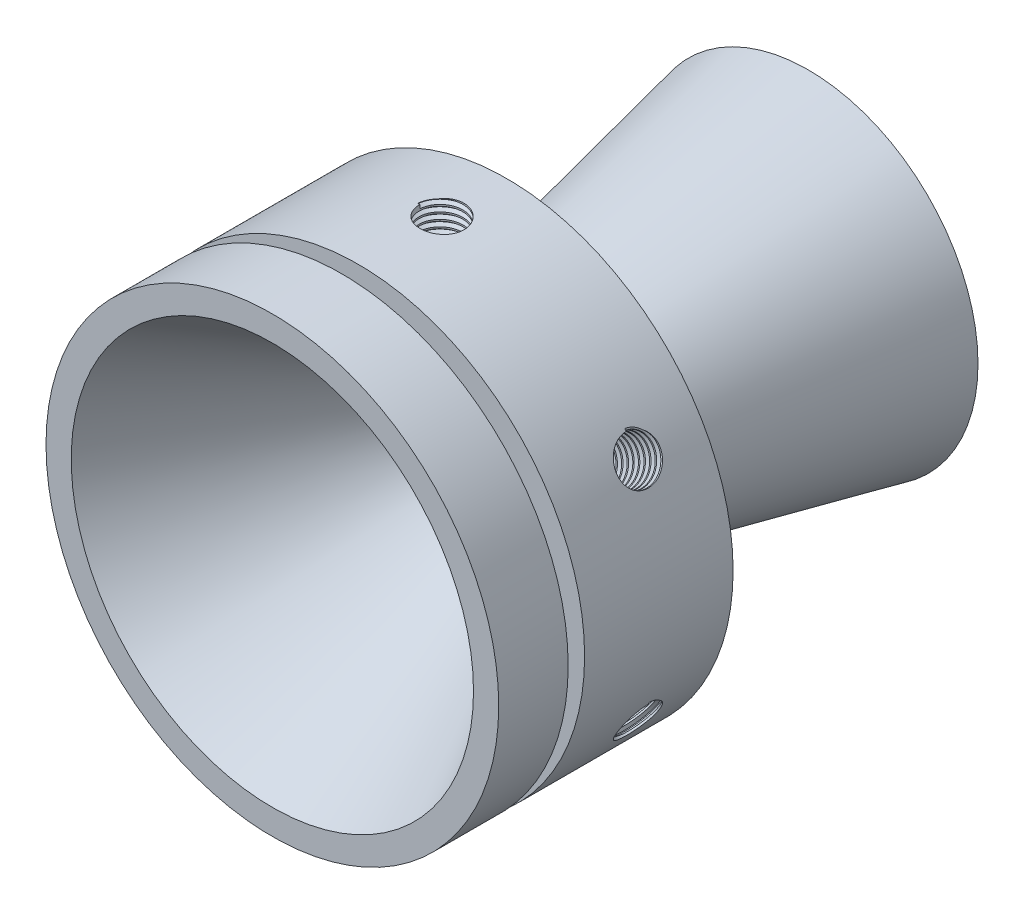
SolidWorks part; units mm, degrees
material "ASTM A53"
ref_plane "Alzado" through (0, 0, 0) normal (0, 0, 1) x (1, 0, 0)
ref_plane "Planta" through (0, 0, 0) normal (0, 1, 0) x (1, 0, 0)
ref_plane "Vista lateral" through (0, 0, 0) normal (1, 0, 0) x (0, 0, -1)
sketch "Croquis2" plane through (0, 0, 0) normal (1, 0, 0) x (0, 0, -1)
  line L0 (-14.0172, 0) -> (56.1534, 0) construction
  line L1 (0, 15.54) -> (18.1077, 5.0855)
  line L2 (18.1077, 5.0855) -> (42.0355, 10.1715)
  line L3 (0, 15.54) -> (0, 17.4892)
  line L4 (0, 17.4892) -> (5.365, 17.4892)
  line L5 (18.1077, 17.4892) -> (18.1077, 8.1525)
  line L6 (18.1077, 8.1525) -> (41.4117, 13.1059)
  line L7 (41.4117, 13.1059) -> (42.0355, 10.1715)
  line L8 (5.365, 17.4892) -> (5.365, 15.4572)
  line L9 (5.365, 15.4572) -> (6.635, 15.4572)
  line L10 (6.635, 15.4572) -> (6.635, 17.4892)
  line L11 (6.635, 17.4892) -> (18.1077, 17.4892)
  point P14 (6, 15.4572)
  point P15 (13.1077, 17.4892)
  dimension "D1" = 12
  dimension "D2" = 30
  dimension "D3" = 10.171
  dimension "D4" = 31.08
  dimension "D5" = 20.343
  dimension "D6" = 3
  dimension "D7" = 34.9784
  dimension "D8" = 6
  dimension "D9" = 2.032
  dimension "D10" = 1.27
  dimension "D11" = 5
revolve "Revolución1" add sketch "Croquis2" angle 360 about L0
ref_plane "Plano1" through (0, 17.4892, 0) normal (0, 1, 0) x (1, 0, 0)
sketch "Croquis3" plane through (0, 17.4892, 0) normal (0, 1, 0) x (1, 0, 0)
  line L0 (17.4892, 18.1077) -> (-17.4892, 18.1077) construction
  point P0 (0, 13.1077)
  dimension "D1" = 5
hole_wizard "Taladro de margen para M31" positions "Croquis3" profile "Croquis5" hole size "M3" standard "Ansi Metric"
sketch "Croquis5" plane through (0, 17.4892, -13.1077) normal (1, 0, 0) x (0, 0, 1)
  line L0 (0, 0) -> (0, 6.0215)
  line L1 (0, 6.0215) -> (1.7, 5)
  line L2 (1.7, 5) -> (1.7, 0)
  line L5 (1.7, 0) -> (0, 0)
  line L10 (0, 6.0215) -> (-1.7, 5) construction
  line L11 (0, -6.35) -> (0, 107.95) construction
  dimension "Diámetro de taladro" = 3.4
  dimension "Profundidad de taladro" = 5
  dimension "Ángulo de perforador" = 118
thread "Rosca1" pitch 0.5 method cut profile "Perfil de rosca1" start angle 0, offset 0, length 4.5, pitch 0.5, diameter 3.4
ref_plane "Plano2" through (-1.7, 17.4892, -13.1077) normal (0, 0, 1) x (-1, 0, 0)
sketch "Perfil de rosca1" plane through (-1.7, 17.4892, -13.1077) normal (0, 0, 1) x (-1, 0, 0)
  line L0 (0, 0) -> (0, 0.5) construction
  line L1 (0, 0) -> (0.2706, 0.1562)
  line L2 (0.2706, 0.1562) -> (0.2706, 0.2187)
  line L3 (0.2706, 0.2187) -> (0, 0.375)
  line L4 (0.2706, 0.1875) -> (0, 0.1875) construction
  line L11 (0, 0) -> (0, 0.375)
  point P2 (0, 0)
  dimension "Pitch" = 0.5
  dimension "Profile_Angle" = 60
  dimension "Profile_Land" = 0.0625
  dimension "Profile_Height" = 0.2706
pattern_circular "MatrizC1" count 6 over 360 about axis through (0, 0, 14.0172) along (0, 0, 1) of "Taladro de margen para M31" reverse direction yes
pattern_circular "MatrizC2" count 6 over 360 about axis through (0, 0, 14.0172) along (0, 0, 1) of "Rosca1" reverse direction yes
equation "\"Dexit\"= 20.343"
equation "\"D5@Croquis2\"=\"Dexit\""
equation "\"DinnerCase\"= 35.08"
equation "\"D7@Croquis2\"=\"DinnerCaseReal\""
equation "\"RadialClearance\"= 0.002pulgadas"
equation "\"DinnerCaseReal\"= \"DinnerCase\" - \"RadialClearance\" * 2"
equation "\"OringXlocation\"= 6"
equation "\"D8@Croquis2\"=\"OringXlocation\""
equation "\"G\"= 0.05pulgadas'O-ring widht gland"
equation "\"D9@Croquis2\"=\"D\""
equation "\"D\"= 0.08pulgadas'O-ring depth gland"
equation "\"ScrewXlocation\"= 5"
equation "\"D11@Croquis2\"=\"ScrewXlocation\""
equation "\"NozzleBellThickness\"=3"
equation "\"D6@Croquis2\"=\"NozzleBellThickness\""
equation "\"D1@Croquis3\"=\"ScrewXlocation\""
equation "\"D10@Croquis2\"=\"G\""
